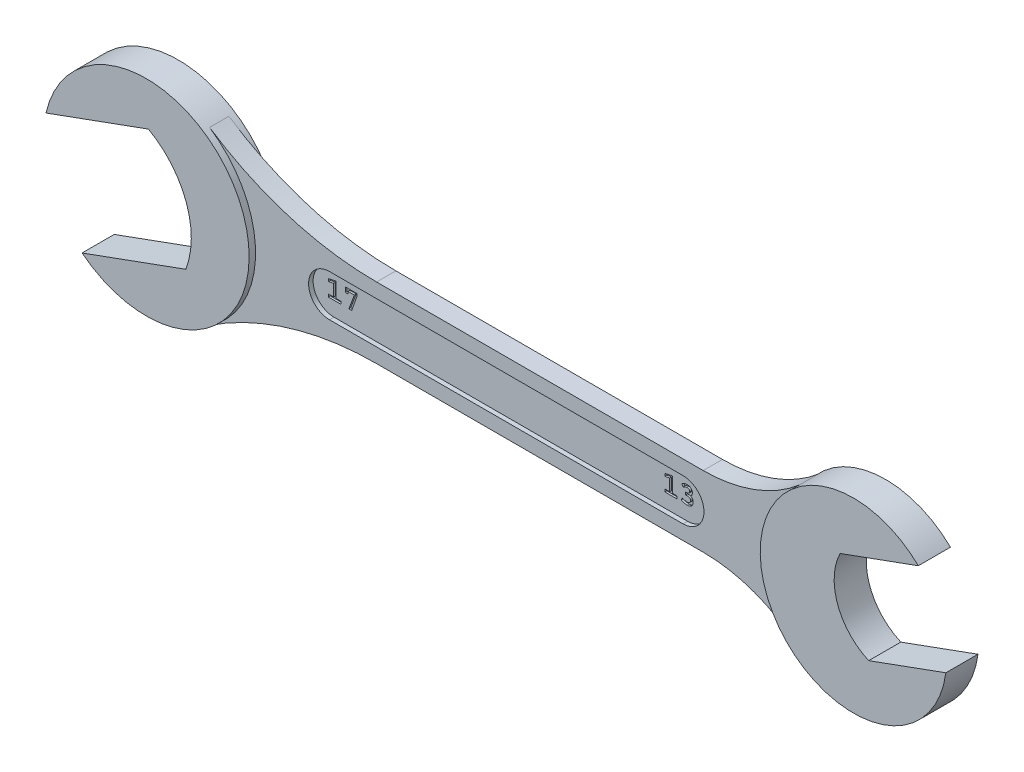
SolidWorks part; units mm, degrees
ref_plane "Front Plane" through (0, 0, 0) normal (0, 0, 1) x (1, 0, 0)
ref_plane "Top Plane" through (0, 0, 0) normal (0, 1, 0) x (1, 0, 0)
ref_plane "Right Plane" through (0, 0, 0) normal (1, 0, 0) x (0, 0, -1)
sketch "Sketch1" plane through (0, 0, 0) normal (0, 0, 1) x (1, 0, 0)
  line L0 (-115.4549, 23.5049) -> (-19.9549, 23.5049) construction
  line L1 (-87.9549, 23.5049) -> (-32.9549, 23.5049) construction
  line L2 (-87.9549, 26.7549) -> (-32.9549, 26.7549)
  line L3 (-87.9549, 20.2549) -> (-32.9549, 20.2549)
  line L4 (-87.9549, 23.5049) -> (-32.9549, 23.5049) construction
  line L5 (-80.6303, 29.0049) -> (-29.827, 29.0049)
  line L6 (-80.6303, 18.0049) -> (-29.827, 18.0049)
  line L7 (-8.2299, 23.5049) -> (-5.4549, 23.5049) construction
  line L8 (-131.0559, 27.056) -> (-115.1191, 32.8565)
  line L12 (-7.5276, 29.4839) -> (4.6409, 33.9128)
  line L14 (-125.4451, 11.0071) -> (-109.3048, 16.8817)
  line L15 (-3.0813, 17.2679) -> (8.9244, 21.6376)
  arc A0 (-125.4451, 11.0071) -> (-131.0559, 27.056) centre (-115.4549, 23.5049) ccw
  arc A1 (4.6409, 33.9128) -> (8.9244, 21.6376) centre (-5.4549, 23.5049) ccw
  arc A3 (-7.5276, 29.4839) -> (-3.0813, 17.2679) centre (0.5451, 25.5049) ccw
  arc A4 (-87.9549, 26.7549) -> (-87.9549, 20.2549) centre (-87.9549, 23.5049) ccw
  arc A5 (-32.9549, 20.2549) -> (-32.9549, 26.7549) centre (-32.9549, 23.5049) ccw
  arc A8 (-106.6106, 36.8383) -> (-80.6303, 29.0049) centre (-80.6303, 76.0049) ccw
  arc A9 (-29.827, 29.0049) -> (-14.8788, 34.5249) centre (-29.827, 52.0049) ccw
  arc A10 (-14.8788, 12.4849) -> (-29.827, 18.0049) centre (-29.827, -4.9951) ccw
  arc A12 (-80.6303, 18.0049) -> (-106.6106, 10.1716) centre (-80.6303, -28.9951) ccw
  arc A14 (-109.3048, 16.8817) -> (-115.1191, 32.8565) centre (-121.4549, 21.5049) ccw
  point P8 (-60.4549, 23.5049)
  point P17 (-5.6538, -0.0734)
  point P18 (-121.4549, 21.5049)
  point P19 (0.5451, 25.5049)
  point P33 (-9.6815, 23.5357)
  point P36 (-9.2318, 15.5288)
  point P37 (0, 0)
  dimension "D2" = 32
  dimension "D3" = 29
  dimension "D7" = 55
  dimension "D8" = 18
  dimension "D13" = 55
  dimension "D14" = 20
  dimension "D1" = 110
  dimension "D4" = 2
  dimension "D5" = 6
  dimension "D6" = 2
  dimension "D9" = 6.5
  dimension "D10" = 6
  dimension "D11" = 11
  dimension "D12" = 5.5
extrude "Boss-Extrude1" add sketch "Sketch1" along normal mid plane 5 contours A14 L14 A0 L8 | A3 L12 A1 L15 region at (-99.9046, 23.5049, 0) region at (-8.0603, 22.6343, 0)
extrude "Boss-Extrude2" add sketch "Sketch1<3>" along normal mid plane 3 contours A12 L6 A10 A1 A9 L5 A8 A0 A5 L3 A4 L2 region at (-55.2287, 28.0496, 0)
sketch "Sketch1<3>" plane through (0, 0, 0) normal (0, 0, 1) x (1, 0, 0) same geometry as "Sketch1"
extrude "Boss-Extrude3" add sketch "Sketch1<4>" along normal mid plane 1.6 contours L3 A5 L2 A4 region at (-60.4549, 23.5049, 0)
sketch "Sketch1<4>" plane through (0, 0, 0) normal (0, 0, 1) x (1, 0, 0) same geometry as "Sketch1"
sketch "Sketch2" plane through (0, 0, 0.8) normal (0, 0, 1) x (1, 0, 0)
  text T0 "<b>17</b>" font "Courier Std" height in points 10
  text T1 "<b>13</b>" font "Courier Std" height in points 10
  point P2 (0, 0)
extrude "Cut-Extrude1" cut sketch "Sketch2" against normal blind 0.3
